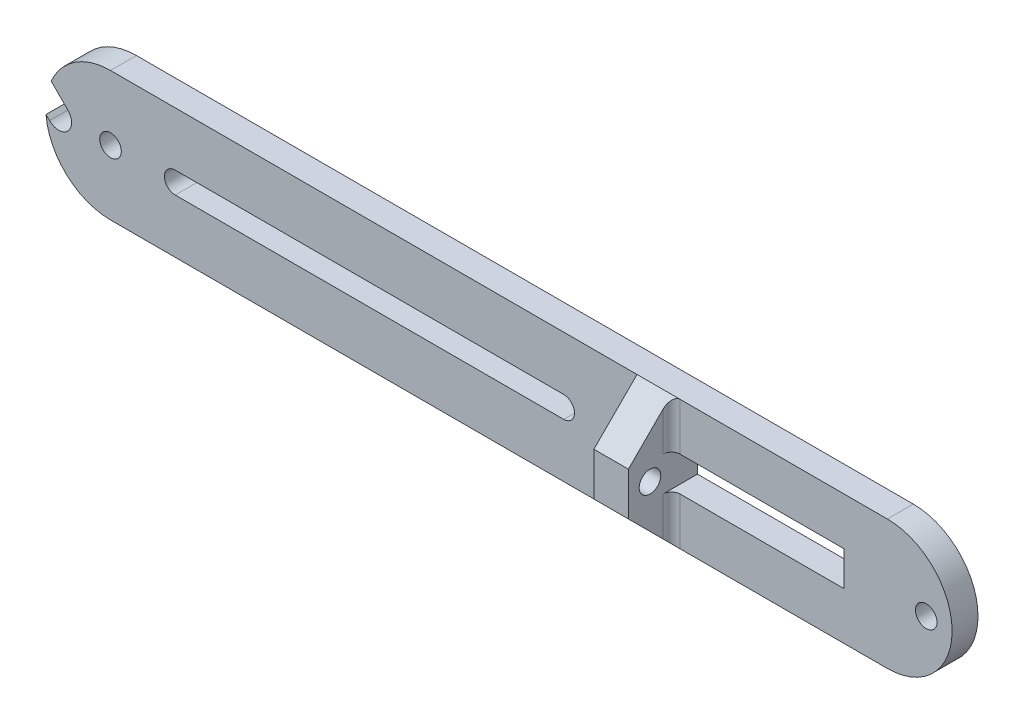
SolidWorks part; units mm, degrees
ref_plane "Plan de face" through (0, 0, 0) normal (0, 0, 1) x (1, 0, 0)
ref_plane "Plan de dessus" through (0, 0, 0) normal (0, 1, 0) x (1, 0, 0)
ref_plane "Plan de droite" through (0, 0, 0) normal (1, 0, 0) x (0, 0, -1)
sketch "Esquisse1" plane through (0, 0, 0) normal (0, 0, 1) x (1, 0, 0)
  line L0 (-74.3787, 0) -> (69.7437, 0) construction
  line L1 (0, 0) -> (0, 19.0596) construction
  line L2 (90, -15) -> (-90, -15)
  line L3 (90, 15) -> (-90, 15)
  line L4 (0, -2.5) -> (-75, -2.5)
  line L5 (40, -4) -> (80, -4)
  line L6 (40, -4) -> (40, 4)
  line L7 (40, 4) -> (80, 4)
  line L8 (80, -4) -> (80, 4)
  line L9 (40, -4) -> (80, 4) construction
  line L10 (40, 4) -> (80, -4) construction
  line L11 (0, 2.5) -> (-75, 2.5)
  line L12 (15, 0) -> (15, 2.5) construction
  line L13 (-1.729, 0) -> (-1.729, 2.5) construction
  line L14 (0, 2.5) -> (15, 2.5)
  line L15 (15, -2.5) -> (0, -2.5)
  arc A0 (90, -15) -> (90, 15) centre (90, 0) ccw
  circle A1 centre (99, 0) radius 2.5
  circle A2 centre (-90, 0) radius 2.5
  arc A3 (-90, -15) -> (-90, 15) centre (-90, 0) cw
  arc A5 (-75, 2.5) -> (-75, -2.5) centre (-75, 0) ccw
  arc A6 (15, -2.5) -> (15, 2.5) centre (15, 0) ccw
  point P4 (60, 0)
  point P17 (0, -15)
  point P20 (0, 15)
  dimension "D1" = 30
  dimension "D3" = 9
  dimension "D7" = 15
  dimension "D8" = 75
  dimension "D2" = 5
  dimension "D12" = 5
  dimension "D4" = 8
  dimension "D5" = 40
  dimension "D6" = 60
extrude "Boss.-Extru.1" add sketch "Esquisse1" along normal blind 6
sketch "Esquisse2" plane through (40, 0, 0) normal (1, 0, 0) x (0, 0, -1)
  line L0 (0, -4) -> (-6, 4) construction
  line L1 (-6, 4) -> (-6, 0) construction
  line L2 (-6, 4) -> (-6, -4) construction
  line L3 (-6, 0) -> (-15.5036, 0) construction
  line L4 (-6, 15) -> (-6, -15) construction
  line L6 (-16, 5) -> (-16, -5)
  line L8 (-6, 5) -> (-6, -5)
  line L9 (-16, 5) -> (-6, -5) construction
  line L10 (-16, -5) -> (-6, 5) construction
  line L11 (-6, -15) -> (-16, -5)
  line L12 (-6, -15) -> (-6, -5)
  line L13 (-6, 5) -> (-6, 15)
  line L14 (-6, 15) -> (-16, 5)
  circle A0 centre (-11, 0) radius 2.5
  point P7 (-11, 0)
  dimension "D3" = 5
  dimension "D1" = 10
  dimension "D2" = 10
extrude "Boss.-Extru.2" add sketch "Esquisse2" against normal blind 8
fillet "Congé2" radius 2 2 edges
sketch "Esquisse3" plane through (32, 0, 0) normal (-1, 0, 0) x (0, 0, 1)
  line L0 (11, 0) -> (11, 4) construction
  line L1 (11, 0) -> (14.4641, 2) construction
  line L2 (11, 0) -> (14.4641, -2) construction
  line L3 (11, 4) -> (14.4641, 2)
  line L4 (14.4641, 2) -> (14.4641, -2)
  line L5 (14.4641, -2) -> (11, -4)
  line L6 (7.5359, 2) -> (7.5359, -2)
  line L7 (11, 4) -> (7.5359, 2)
  line L8 (7.5359, -2) -> (11, -4)
  dimension "D2" = 60
  dimension "D3" = 60
extrude "Enlèv. mat.-Extru.1" cut sketch "Esquisse3" against normal blind 4
sketch "Esquisse4" plane through (0, 0, 6) normal (0, 0, 1) x (1, 0, 0)
  line L0 (-90, 0) -> (-105, 0) construction
  line L1 (-105, 0) -> (-102, 0) construction
  line L2 (-102, 0) -> (-104.1213, -2.1213) construction
  line L3 (-104.1213, -2.1213) -> (-99.8787, 2.1213)
  line L4 (-104.1213, -2.1213) -> (-99.8787, 2.1213)
  line L5 (-104.1213, -2.1213) -> (-108.504, 2.2614)
  line L6 (-99.8787, 2.1213) -> (-104.2614, 6.504)
  line L7 (-108.504, 2.2614) -> (-104.2614, 6.504)
  arc A0 (-90, 15) -> (-90, -15) centre (-90, 0) ccw construction
  circle A1 centre (-102, 0) radius 3
  arc M9 (-90, 15) -> (-90, -15) centre (-90, 0) ccw
  dimension "D1" = 3
  dimension "D2" = 45
extrude "Enlèv. mat.-Extru.4" cut sketch "Esquisse4" against normal blind 10 contours L3 A1 | A1 L6 M9 | A1 L5 M9 | L3 A1 region at (-102.9003, 0.9003, 6) region at (-101.0997, -0.9003, 6) region at (-104.7977, -1.1965, 6) region at (-103.2777, 3.6386, 6)
